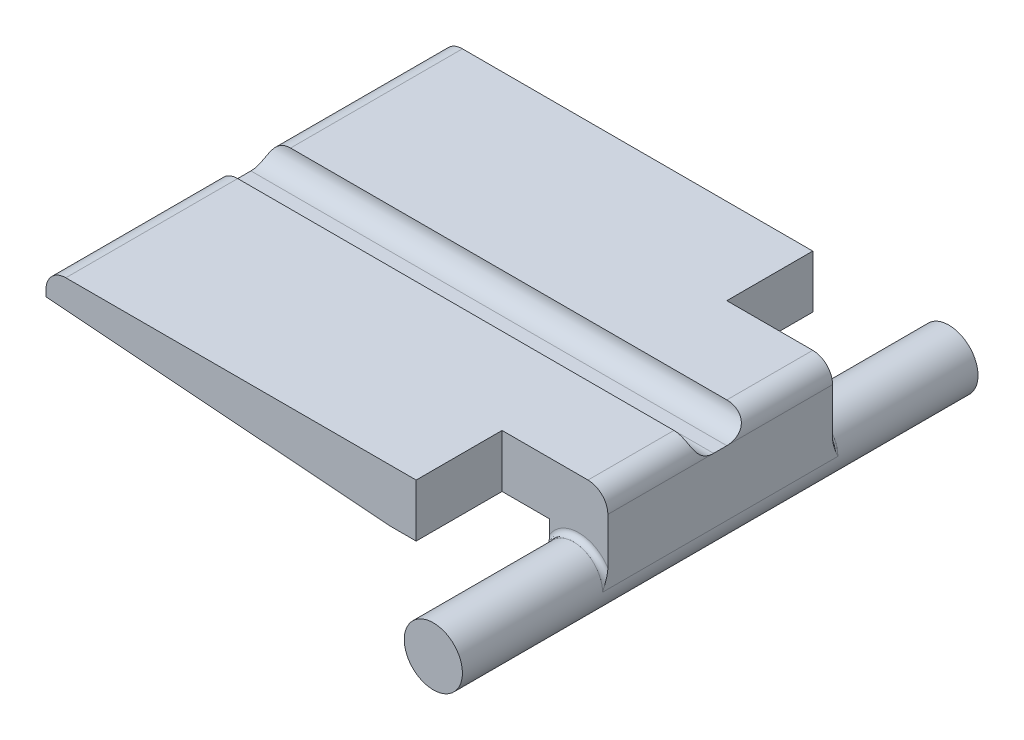
SolidWorks part; units mm, degrees
ref_plane "Front Plane" through (0, 0, 0) normal (0, 0, 1) x (1, 0, 0)
ref_plane "Top Plane" through (0, 0, 0) normal (0, 1, 0) x (1, 0, 0)
ref_plane "Right Plane" through (0, 0, 0) normal (1, 0, 0) x (0, 0, -1)
sketch "Sketch1" plane through (0, 0, 0) normal (0, 1, 0) x (1, 0, 0)
  line L0 (7, 4.25) -> (11, 4.25)
  line L1 (-7, -7.5) -> (7, -7.5)
  line L2 (-7, -7.5) -> (-7, 7.5)
  line L3 (-7, 7.5) -> (7, 7.5)
  line L4 (7, -7.5) -> (7, -4.25)
  line L5 (-7, -7.5) -> (7, 7.5) construction
  line L6 (-7, 7.5) -> (7, -7.5) construction
  line L10 (11, 4.25) -> (11, -4.25)
  line L13 (7, 4.25) -> (7, 7.5)
  line L17 (7, -4.25) -> (11, -4.25)
  point P0 (0, 0)
  point P6 (11, 0)
  dimension "D1" = 15
  dimension "D2" = 14
  dimension "D3" = 8.5
  dimension "D4" = 4
extrude "Boss-Extrude1" add sketch "Sketch1" along normal blind 2
sketch "Sketch2" plane through (0, 2, 0) normal (0, 1, 0) x (1, 0, 0)
  line L1 (-12.5, 1) -> (12.5, 1)
  line L2 (-12.5, 1) -> (-12.5, -1)
  line L3 (-12.5, -1) -> (12.5, -1)
  line L4 (12.5, 1) -> (12.5, -1)
  line L5 (-12.5, 1) -> (12.5, -1) construction
  line L6 (-12.5, -1) -> (12.5, 1) construction
  point P0 (0, 0)
  dimension "D1" = 25
  dimension "D2" = 2
extrude "Cut-Extrude1" cut sketch "Sketch2" against normal blind 0.75
sketch "Sketch3" plane through (0, 0, 0) normal (0, -1, 0) x (1, 0, 0)
  line L0 (11, -4.25) -> (7, -4.25) construction
  line L1 (11, 4.25) -> (8.8, 4.25)
  line L2 (11, 4.25) -> (11, -4.25)
  line L3 (11, -4.25) -> (8.8, -4.25)
  line L4 (8.8, 4.25) -> (8.8, -4.25)
  dimension "D1" = 2.2
extrude "Boss-Extrude2" add sketch "Sketch3" along normal blind 1.2
sketch "Sketch4" plane through (0, 0, 0) normal (0, 0, 1) x (1, 0, 0)
  line L0 (11, -1.2) -> (8.8, -1.2) construction
  circle A0 centre (9.9, -1.2) radius 1.1
extrude "Boss-Extrude3" add sketch "Sketch4" along normal mid plane 19.5
fillet "Fillet1" radius 0.75 2 edges at (2, 1.25, -1) (2, 1.25, 1)
fillet "Fillet2" radius 0.75 4 edges at (11, 2, -2.625) (11, 2, 2.625) (-7, 2, -4.25) (-7, 2, 4.25)
chamfer "Chamfer1" distance 13 distance2 1 1 edges at (-7, 0, 0) first distance on face at (3.95, 0, 0)
fillet "Fillet3" radius 0.2 2 edges at (9.9, -0.1, 4.25) (9.9, -0.1, -4.25)
